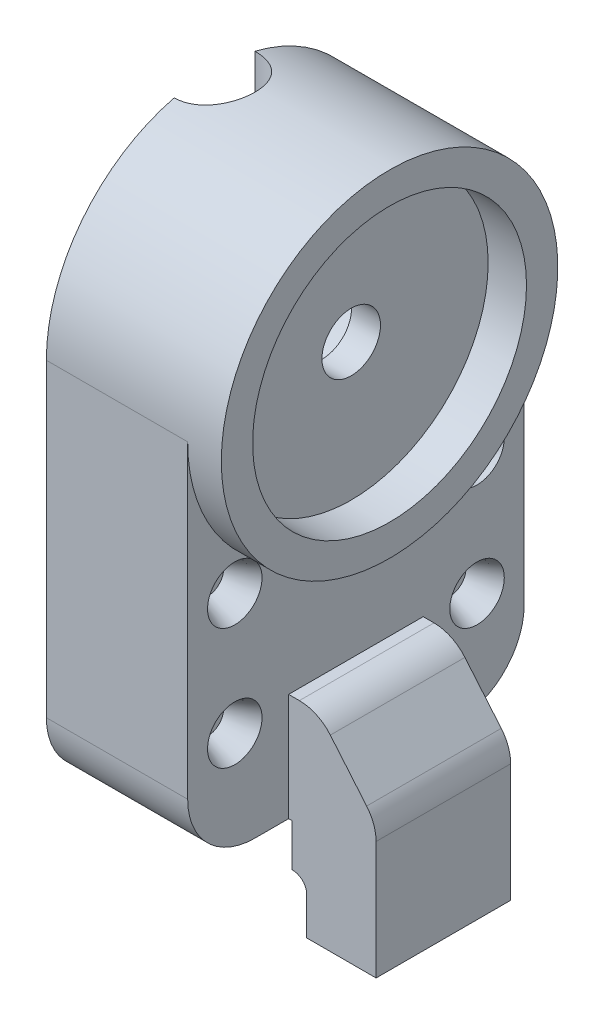
SolidWorks part; units mm, degrees
material "ABS"
ref_plane "Alzado" through (0, 0, 0) normal (0, 0, 1) x (1, 0, 0)
ref_plane "Planta" through (0, 0, 0) normal (0, 1, 0) x (1, 0, 0)
ref_plane "Vista lateral" through (0, 0, 0) normal (1, 0, 0) x (0, 0, -1)
sketch "Croquis1" plane through (0, 0, 0) normal (0, 1, 0) x (1, 0, 0)
  line L5 (0, 0) -> (10.5, 0)
  line L6 (0, 0) -> (0, 25)
  line L7 (0, 25) -> (10.5, 25)
  line L8 (10.5, 0) -> (10.5, 25)
  dimension "D1" = 25
  dimension "D2" = 10.5
extrude "Saliente-Extruir1" add sketch "Croquis1" along normal blind 28
sketch "Croquis2" plane through (0, 0, 0) normal (-1, 0, 0) x (0, 0, 1)
  line L1 (-25, 28) -> (0, 28) construction
  circle A0 centre (-12.5, 28) radius 12.5
  dimension "D1" = 25
extrude "Saliente-Extruir2" add sketch "Croquis2" against normal blind 13
sketch "Croquis3" plane through (0, 0, 0) normal (-1, 0, 0) x (0, 0, 1)
  line L1 (-25, 0) -> (0, 0) construction
  line L2 (-12.5, 0.5) -> (-4.5, 0.5) construction
  line L3 (-4.5, 0.5) -> (-4.5, 3.5) construction
  line L4 (-4.5, 3.5) -> (-6.5, 3.5) construction
  line L5 (-6.5, 3.5) -> (-6.5, 10.5) construction
  line L6 (-6.5, 10.5) -> (-4.5, 10.5) construction
  line L7 (-4.5, 10.5) -> (-4.5, 14.5) construction
  line L8 (-4.5, 14.5) -> (-12.5, 14.5) construction
  line L9 (-4, 0.5) -> (-4, 4)
  line L10 (-4, 4) -> (-6, 4)
  line L11 (-6, 4) -> (-6, 10)
  line L12 (-6, 10) -> (-4, 10)
  line L13 (-4, 10) -> (-4, 15)
  line L14 (-4, 15) -> (-9.5, 15)
  line L16 (-12.5, 0) -> (-12.5, 41)
  line L17 (-12.5, 0) -> (-4, 0)
  line L18 (-4, 0) -> (-4, 0.5)
  line L20 (-4, 15) -> (-12.5, 15) construction
  line L21 (-12.5, 41) -> (-9.5, 41)
  line L22 (-9.5, 41) -> (-9.5, 15)
  point P27 (-12.5, 0)
  dimension "D1" = 8
  dimension "D2" = 3
  dimension "D3" = 6
  dimension "D4" = 7
  dimension "D5" = 4
  dimension "D6" = 0.5
  dimension "D7" = 0.5
  dimension "D8" = 3
  dimension "D9" = 41
revolve "Cortar-Revolución1" cut sketch "Croquis3" angle 360 about L16
fillet "Redondeo1" radius 5 2 edges at (5.25, 0, -25) (5.25, 0, 0)
sketch "Croquis4" plane through (0, 15, 0) normal (0, -1, 0) x (1, 0, 0)
  line L1 (0, -18.2735) -> (5, -15.3868) construction
  line L2 (5, -15.3868) -> (5, -9.6132) construction
  line L3 (5, -9.6132) -> (0, -6.7265) construction
  line L4 (0, -6.7265) -> (-5, -9.6132) construction
  line L5 (-5, -9.6132) -> (-5, -15.3868) construction
  line L6 (-5, -15.3868) -> (0, -18.2735) construction
  line L7 (0, -18.6776) -> (5.35, -15.5888)
  line L8 (5.35, -15.5888) -> (5.35, -9.4112)
  line L9 (5.35, -9.4112) -> (0, -6.3224)
  line L10 (0, -6.3224) -> (-5.35, -9.4112)
  line L11 (-5.35, -9.4112) -> (-5.35, -15.5888)
  line L12 (-5.35, -15.5888) -> (0, -18.6776)
  line L13 (0, -21) -> (0, -15.5) construction
  circle A0 centre (0, -12.5) radius 5 construction
  dimension "D1" = 10
  dimension "D2" = 0.35
extrude "Cortar-Extruir1" cut sketch "Croquis4" against normal blind 13
sketch "Croquis5" plane through (0, 0, 0) normal (-1, 0, 0) x (0, 0, 1)
  circle A0 centre (-12.5, 28) radius 9.915
  dimension "D1" = 19.83
extrude "Cortar-Extruir2" cut sketch "Croquis5" against normal offset from surface (8 mm away) 5 up to face at (13, 28, 0)
sketch "Croquis8" plane through (0, 0, 0) normal (-1, 0, 0) x (0, 0, 1)
  line L6 (-25, 28) -> (-25, 5) construction
  line L7 (0, 28) -> (0, 5) construction
  line L8 (-6.3224, 15) -> (-4, 15) construction
  circle A0 centre (-21.5, 16.5) radius 1.175
  circle A1 centre (-3.5, 16.5) radius 1.175
  circle A2 centre (-3.5, 7.5) radius 1.175
  circle A3 centre (-21.5, 7.5) radius 1.175
  dimension "D1" = 3.5
  dimension "D2" = 2.35
  dimension "D3" = 3.5
  dimension "D4" = 1.5
  dimension "D5" = 9
extrude "Cortar-Extruir5" cut sketch "Croquis8" against normal through all
ref_plane "Plano1" through (0, 0, -12.5) normal (0, 0, 1) x (1, 0, 0)
sketch "Croquis10" plane through (0, 0, -12.5) normal (0, 0, 1) x (1, 0, 0)
  line L8 (10.5, 28) -> (10.5, 5) construction
  line L9 (10.5, 8) -> (17, 8)
  line L10 (10.5, 8) -> (10.5, -7)
  line L11 (10.5, -7) -> (17, -7)
  line L12 (17, 8) -> (17, -7)
  line L13 (10.5, 0) -> (4, 0) construction
  dimension "D1" = 8
  dimension "D2" = 15
  dimension "D3" = 6.5
extrude "Saliente-Extruir3" add sketch "Croquis10" along normal mid plane 10
sketch "Croquis11" plane through (0, -7, 0) normal (0, -1, 0) x (1, 0, 0)
  line L4 (10.5, -17.5) -> (17, -17.5)
  line L5 (17, -17.5) -> (17, -7.5)
  line L6 (17, -7.5) -> (10.5, -7.5)
  line L12 (10.5, -7.5) -> (10.5, -17.5)
  line L13 (10.5, -17.5) -> (10.7435, -17.5)
  line L15 (10.7435, -7.5) -> (10.5, -7.5)
  line L16 (10.5, -7.5) -> (10.5, -17.5)
  arc A3 (10.7435, -17.5) -> (10.7435, -7.5) centre (0, -12.5) ccw
  arc A4 (4, -20) -> (4, -5) centre (0, -12.5) ccw construction
  dimension "D1" = 11.85
  dimension "D2" = 0
extrude "Cortar-Extruir6" cut sketch "Croquis11" against normal up to surface (7 mm away) up to face at (9.0833, 0, -12.5)
sketch "Croquis12" plane through (0, -7, 0) normal (0, -1, 0) x (1, 0, 0)
  line L0 (-12.35, -10.5693) -> (-15.5, -30.719) construction
  line L2 (12.35, -10.5693) -> (15.5, -30.719) construction
  line L3 (10.7435, -17.5) -> (17, -17.5)
  line L4 (17, -7.5) -> (10.7435, -7.5)
  line L5 (17, -17.5) -> (17, -7.5)
  line L7 (17, -7.5) -> (10.7435, -7.5)
  line L9 (15.5, -30.719) -> (-15.5, -30.719) construction
  line L10 (11.135, -6.8201) -> (-11.135, -6.8201) construction
  line L15 (10.7435, -17.5) -> (17, -17.5)
  line L16 (12.6958, -10.5153) -> (13.7877, -17.5)
  line L17 (12.6958, -10.5153) -> (15.8458, -30.665) construction
  line L23 (17, -17.5) -> (17, -7.5)
  arc A1 (12.35, -10.5693) -> (11.135, -6.8201) centre (0, -12.5) ccw construction
  arc A2 (12.6958, -10.5153) -> (11.8373, -7.5) centre (0, -12.5) ccw
  arc A4 (-11.135, -6.8201) -> (-12.35, -10.5693) centre (0, -12.5) ccw construction
  arc A7 (12.6958, -10.5153) -> (11.4468, -6.661) centre (0, -12.5) ccw construction
  arc A9 (10.7435, -17.5) -> (10.7435, -7.5) centre (0, -12.5) ccw
  arc A10 (10.7435, -17.5) -> (10.7435, -7.5) centre (0, -12.5) ccw
  point P5 (0, -30.719)
  line M19 (10.7435, -17.5) -> (17, -17.5)
  arc M26 (10.7435, -7.5) -> (10.7435, -17.5) centre (0, -12.5) cw
  dimension "D1" = 0
  dimension "D2" = 25
  dimension "D3" = 31
  dimension "D4" = 24.7
  dimension "D5" = 22.27
  dimension "D6" = 6.8201
  dimension "D7" = 11.135
  dimension "D8" = 0.35
extrude "Cortar-Extruir7" cut sketch "Croquis12" against normal blind 3.85 contours L16 A2 L7 M26 M19 region at (12.2803, -7, -13.4906)
chamfer "Chaflán1" distance 4.3 angle 50 1 edges at (17, 8, -12.5) first distance on face at (13.75, 8, -12.5)
fillet "Redondeo2" radius 1 2 edges at (12.3589, -3.15, -8.9814) (13.2418, -3.15, -14.0076)
fillet "Redondeo3" radius 3 2 edges at (17, 2.8755, -12.5) (12.7, 8, -12.5)
sketch "Croquis13" plane through (13, 0, 0) normal (1, 0, 0) x (0, 0, -1)
  line L0 (10.2027, 30.2989) -> (10.8524, 42.3389) construction
  line L1 (14.1466, 42.3558) -> (14.9306, 30.1575) construction
  line L2 (9.25, 28) -> (15.75, 28)
  line L3 (14.1466, 13.6442) -> (14.9306, 25.8425) construction
  line L4 (10.2027, 25.7011) -> (10.8524, 13.6611) construction
  line L5 (9.8602, 25.5522) -> (10.5029, 13.6422)
  line L6 (14.4959, 13.6217) -> (15.2724, 25.7035)
  line L7 (14.4959, 42.3783) -> (15.2724, 30.2965)
  line L8 (9.8602, 30.4478) -> (10.5029, 42.3578)
  arc A0 (10.2027, 30.2989) -> (10.2027, 25.7011) centre (12.5, 28) ccw construction
  arc A1 (14.1466, 42.3558) -> (10.8524, 42.3389) centre (12.5, 42.25) ccw construction
  arc A3 (14.9306, 25.8425) -> (14.9306, 30.1575) centre (12.5, 28) ccw construction
  arc A4 (14.1466, 13.6442) -> (10.8524, 13.6611) centre (12.5, 13.75) cw construction
  arc A5 (9.8602, 30.4478) -> (9.8602, 25.5522) centre (12.5, 28) ccw
  arc A6 (14.4959, 13.6217) -> (10.5029, 13.6422) centre (12.5, 13.75) cw
  arc A7 (15.2724, 25.7035) -> (15.2724, 30.2965) centre (12.5, 28) ccw
  arc A8 (14.4959, 42.3783) -> (10.5029, 42.3578) centre (12.5, 42.25) ccw
  dimension "D1" = 3.3
  dimension "D2" = 0.35
  dimension "D4" = 6.5
  dimension "D3" = 14.25
  dimension "D6" = 4.73
  dimension "D7" = 12.04
extrude "Cortar-Extruir8" cut sketch "Croquis13" against normal up to surface (2.5 mm away) contours L6 A7 L7 L8 A5 L5 region at (13, 28, -9.1602) up to face at (10.5, 7.5, -20.325)
sketch "Croquis14" plane through (10.5, 0, 0) normal (1, 0, 0) x (0, 0, -1)
  circle A0 centre (12.5, 28) radius 3.6
  arc A1 (15.2724, 25.7035) -> (15.2724, 30.2965) centre (12.5, 28) ccw construction
extrude "Cortar-Extruir9" cut sketch "Croquis14" against normal through all
sketch "Croquis15" plane through (10.5, 0, 0) normal (1, 0, 0) x (0, 0, -1)
  circle A0 centre (3.5, 16.5) radius 2.025
  circle A1 centre (3.5, 7.5) radius 2.025
  circle A2 centre (21.5, 7.5) radius 2.025
  circle A3 centre (21.5, 16.5) radius 2.025
  dimension "D1" = 4.05
  dimension "D2" = 4.05
  dimension "D3" = 4.05
  dimension "D4" = 4.05
extrude "Cortar-Extruir10" cut sketch "Croquis15" against normal blind 2 draft 23
ref_axis "Eje1" through (-26.5426, 28, -12.5) along (1, 0, 0)
sketch "Croquis16" plane through (8, 0, 0) normal (-1, 0, 0) x (0, 0, 1)
  circle A0 centre (-12.5, 28) radius 3.6 construction
  circle A1 centre (-12.5, 28) radius 3.6
extrude "Saliente-Extruir4" add sketch "Croquis16" against normal up to surface (2.5 mm away) up to face at (10.5, 16.5, -23.525)
sketch "Croquis17" plane through (10.5, 0, 0) normal (1, 0, 0) x (0, 0, -1)
  circle A0 centre (12.5, 28) radius 12.5
extrude "Saliente-Extruir5" add sketch "Croquis17" along normal up to surface (2.5 mm away) up to face at (13, 28, -17.7502)
sketch "Croquis18" plane through (13, 0, 0) normal (1, 0, 0) x (0, 0, -1)
  circle A0 centre (12.5, 28) radius 2.175
  dimension "D1" = 4.35
extrude "Cortar-Extruir11" cut sketch "Croquis18" against normal through all
sketch "Croquis19" plane through (13, 0, 0) normal (1, 0, 0) x (0, 0, -1)
  circle A0 centre (12.5, 28) radius 10.175
  dimension "D1" = 20.35
extrude "Cortar-Extruir12" cut sketch "Croquis19" against normal blind 2.85
